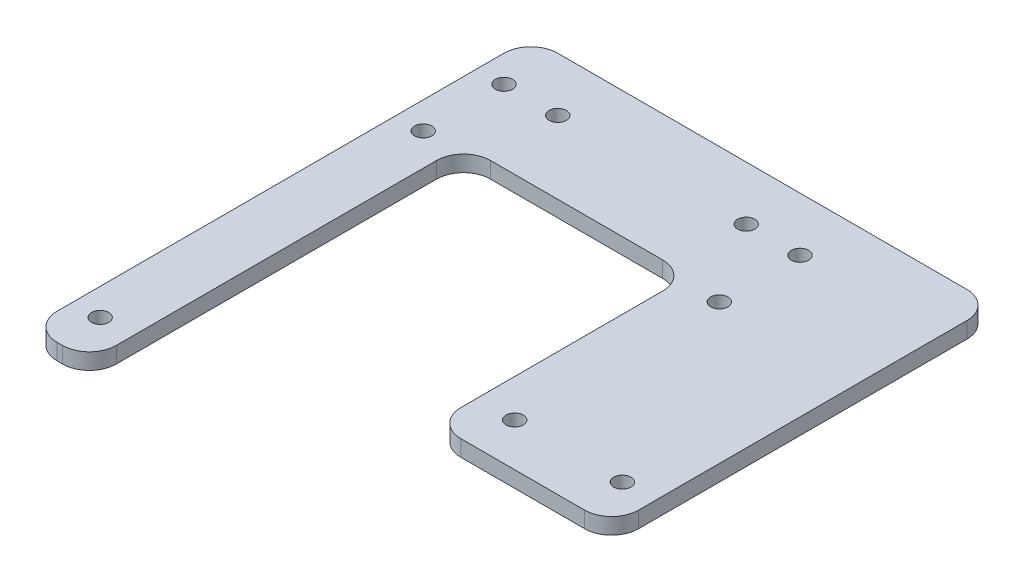
SolidWorks part; units mm, degrees
material "A-玻璃纤维"
ref_plane "前视基准面" through (0, 0, 0) normal (0, 0, 1) x (1, 0, 0)
ref_plane "上视基准面" through (0, 0, 0) normal (0, 1, 0) x (1, 0, 0)
ref_plane "右视基准面" through (0, 0, 0) normal (1, 0, 0) x (0, 0, -1)
sketch "草图1" plane through (0, 0, 0) normal (0, 1, 0) x (1, 0, 0)
  line L0 (0, 420.0815) -> (0, -400.8011) construction
  line L1 (190, 287) -> (101.545, 287)
  line L2 (190, 287) -> (190, 0)
  line L3 (190, -281) -> (144.0917, -281)
  line L4 (-190, 287) -> (-190, 0)
  line L5 (-313.6361, 0) -> (397.123, 0) construction
  line L6 (144.0917, -281) -> (98.6603, -281)
  line L7 (-101.545, 287) -> (-79.6057, 249)
  line L8 (-79.6057, 249) -> (79.6057, 249)
  line L9 (79.6057, 249) -> (101.545, 287)
  line L10 (-98.6603, -281) -> (-74.4115, -239)
  line L12 (-74.4115, -239) -> (74.4115, -239)
  line L13 (-144.0917, -281) -> (-190, -281)
  line L14 (-101.545, 287) -> (-190, 287)
  line L15 (-98.6603, -281) -> (-144.0917, -281)
  line L17 (190, 0) -> (190, -281)
  line L20 (190, 287) -> (190, -281) construction
  line L22 (74.4115, -239) -> (98.6603, -281)
  line L24 (-190, 0) -> (-190, -281)
  line L26 (-190, 287) -> (-190, -281) construction
  line L44 (229.3448, 326.3448) -> (229.3448, -320.3448) construction
  line L45 (-229.3448, 326.3448) -> (-229.3448, -320.3448) construction
  line L46 (-78.8293, 326.3448) -> (-229.3448, 326.3448) construction
  line L47 (-78.8293, 326.3448) -> (-56.89, 288.3448) construction
  line L48 (-56.89, 288.3448) -> (56.89, 288.3448) construction
  line L49 (56.89, 288.3448) -> (78.8293, 326.3448) construction
  line L50 (229.3448, 326.3448) -> (78.8293, 326.3448) construction
  line L51 (-121.376, -320.3448) -> (-229.3448, -320.3448) construction
  line L52 (229.3448, -320.3448) -> (121.376, -320.3448) construction
  line L53 (-98.6603, -281) -> (-121.376, -320.3448) construction
  line L54 (98.6603, -281) -> (121.376, -320.3448) construction
  line L55 (-132.7338, -261.3276) -> (-144.0917, -281) construction
  line L56 (-132.7338, -261.3276) -> (-97.1273, -199.6552) construction
  line L57 (-97.1273, -199.6552) -> (97.1273, -199.6552) construction
  line L58 (97.1273, -199.6552) -> (132.7338, -261.3276) construction
  line L59 (132.7338, -261.3276) -> (144.0917, -281) construction
  point P0 (0, 0)
  point P10 (-110.2073, -274)
  point P13 (-79.8964, -221.5)
  point P14 (79.8964, -221.5)
  point P16 (110.2073, -274)
  point P21 (200, -271.5)
  point P22 (200, 291.5)
  point P23 (-145.7725, 287)
  point P24 (77.0076, 246.5)
  point P25 (-77.0076, 246.5)
  point P27 (-200, 291.5)
  point P28 (-200, -271.5)
  dimension "D1" = 568
  dimension "D2" = 380
  dimension "D3" = 38
  dimension "D4" = 197.3205
  dimension "D5" = 120
  dimension "D6" = 60
  dimension "D7" = 203.09
  dimension "D8" = 42
  dimension "D9" = 287
extrude "基本板" add sketch "草图1" along normal blind 3
sketch "草图2" plane through (0, 3, 0) normal (0, 1, 0) x (1, 0, 0)
  circle A0 centre (0, 0) radius 37.5
  circle A1 centre (38.9711, 22.5) radius 1.6
  circle A3 centre (0, 0) radius 37.5
  circle A5 centre (0, -45) radius 1.6
  circle A6 centre (0, 0) radius 37.5
  circle A7 centre (-38.9711, 22.5) radius 1.6
  point P14 (0, 0)
  point P16 (0, 0)
  dimension "D1" = 75
  dimension "D3" = 3.2
  dimension "D2" = 45
  dimension "D4" = 3
extrude "云台孔" cut sketch "草图2" against normal blind 3 contours A1 | A0 | A5 | A7 region at (0, 3, 0) region at (38.9711, 3, -22.5) region at (0, 3, 45) region at (-38.9711, 3, -22.5)
sketch "草图8" plane through (0, 3, 0) normal (0, 1, 0) x (1, 0, 0)
  line L0 (0, 320.5112) -> (0, -345.0597) construction
  line L13 (82.5, -149) -> (147.5, -149)
  line L14 (-82.5, -149) -> (-147.5, -149)
  line L15 (-82.5, -149) -> (-82.5, -174)
  line L16 (-82.5, -174) -> (-147.5, -174)
  line L17 (-147.5, -149) -> (-147.5, -174)
  line L18 (-82.5, -149) -> (-147.5, -174) construction
  line L19 (-82.5, -174) -> (-147.5, -149) construction
  line L20 (147.5, -149) -> (147.5, -174)
  line L21 (82.5, -149) -> (147.5, -174) construction
  line L22 (82.5, -174) -> (147.5, -149) construction
  line L23 (82.5, -149) -> (82.5, -174)
  line L24 (82.5, -174) -> (147.5, -174)
  point P12 (-115, -161.5)
  dimension "D1" = 230
  dimension "D5" = 174
  dimension "D7" = 25
  dimension "D8" = 65
extrude "减重过线孔" cut sketch "草图8" against normal blind 3
sketch "草图41" plane through (0, 3, 0) normal (0, 1, 0) x (1, 0, 0)
  line L0 (0, 188.4867) -> (0, -152.142) construction
  line L1 (-206.7892, 0) -> (229.7274, 0) construction
  line L2 (-130, 100) -> (-75, 100)
  line L3 (-130, 100) -> (-130, 40)
  line L4 (-130, 40) -> (-75, 40)
  line L5 (-75, 100) -> (-75, 40)
  line L6 (75, 100) -> (75, 40)
  line L7 (130, 40) -> (75, 40)
  line L8 (130, 100) -> (130, 40)
  line L9 (130, 100) -> (75, 100)
  line L10 (130, -100) -> (75, -100)
  line L11 (130, -100) -> (130, -40)
  line L12 (130, -40) -> (75, -40)
  line L13 (75, -100) -> (75, -40)
  line L14 (-75, -100) -> (-75, -40)
  line L15 (-130, -40) -> (-75, -40)
  line L16 (-130, -100) -> (-130, -40)
  line L17 (-130, -100) -> (-75, -100)
  dimension "D1" = 40
  dimension "D2" = 75
  dimension "D3" = 55
  dimension "D4" = 60
extrude "减重过线孔2" cut sketch "草图41" against normal blind 10
sketch "草图10" plane through (0, 3, 0) normal (0, 1, 0) x (1, 0, 0)
  line L0 (0, 320.3944) -> (0, -95.0551) construction
  line L1 (-162.5, 182) -> (-97.5, 182)
  line L2 (-162.5, 182) -> (-162.5, 152)
  line L3 (-162.5, 152) -> (-97.5, 152)
  line L4 (-97.5, 182) -> (-97.5, 152)
  line L5 (-162.5, 182) -> (-97.5, 152) construction
  line L6 (-162.5, 152) -> (-97.5, 182) construction
  line L7 (162.5, 152) -> (97.5, 152)
  line L8 (97.5, 152) -> (97.5, 182)
  line L9 (97.5, 182) -> (162.5, 182)
  line L11 (162.5, 182) -> (162.5, 152)
  point P0 (-130, 167)
  dimension "D1" = 65
  dimension "D2" = 30
  dimension "D3" = 167
  dimension "D4" = 130
  dimension "D5" = 65
extrude "后电机过线孔" cut sketch "草图10" against normal blind 3
sketch "草图11" plane through (0, 3, 0) normal (0, 1, 0) x (1, 0, 0)
  line L0 (-190, 287) -> (-190, -281) construction
  line L1 (-179, 248) -> (-137, 248)
  line L2 (-179, 248) -> (-179, 220)
  line L3 (-179, 220) -> (-137, 220)
  line L4 (-137, 248) -> (-137, 220)
  line L5 (-179, 248) -> (-137, 220) construction
  line L6 (-179, 220) -> (-137, 248) construction
  line L8 (-158, 274.32) -> (-158, 185.5546) construction
  line L9 (-208.9066, 234) -> (-106.7696, 234) construction
  line L10 (-264.4169, 0) -> (335.6364, 0) construction
  line L11 (0, 360.1922) -> (0, -386.7193) construction
  line L12 (179, 248) -> (179, 220)
  line L13 (179, 220) -> (137, 220)
  line L14 (137, 248) -> (137, 220)
  line L15 (179, 248) -> (137, 248)
  line L16 (179, -248) -> (137, -248)
  line L17 (137, -248) -> (137, -220)
  line L18 (179, -220) -> (137, -220)
  line L19 (179, -248) -> (179, -220)
  line L20 (-179, -248) -> (-179, -220)
  line L21 (-179, -220) -> (-137, -220)
  line L22 (-137, -248) -> (-137, -220)
  line L23 (-179, -248) -> (-137, -248)
  circle A0 centre (-153.5, 259) radius 1.6
  circle A1 centre (-162.5, 259) radius 1.6
  circle A2 centre (-153.5, 209) radius 1.6
  circle A3 centre (-162.5, 209) radius 1.6
  circle A4 centre (153.5, 259) radius 1.6
  circle A5 centre (162.5, 259) radius 1.6
  circle A6 centre (153.5, 209) radius 1.6
  circle A7 centre (162.5, 209) radius 1.6
  circle A8 centre (162.5, -209) radius 1.6
  circle A9 centre (153.5, -209) radius 1.6
  circle A10 centre (162.5, -259) radius 1.6
  circle A11 centre (153.5, -259) radius 1.6
  circle A12 centre (-162.5, -209) radius 1.6
  circle A13 centre (-153.5, -209) radius 1.6
  circle A14 centre (-153.5, -259) radius 1.6
  circle A15 centre (-162.5, -259) radius 1.6
  point P0 (-158, 234)
  dimension "D5" = 3.2
  dimension "D1" = 42
  dimension "D2" = 28
  dimension "D3" = 32
  dimension "D4" = 468
  dimension "D6" = 4.5
  dimension "D7" = 25
extrude "悬挂过孔" cut sketch "草图11" against normal blind 3
sketch "草图13" plane through (0, 3, 0) normal (0, 1, 0) x (1, 0, 0)
  line L0 (79.6057, 249) -> (-79.6057, 249) construction
  line L1 (25, 226) -> (-25, 226) construction
  line L2 (25, 226) -> (25, 176) construction
  line L3 (25, 176) -> (-25, 176) construction
  line L4 (-25, 226) -> (-25, 176) construction
  line L5 (25, 226) -> (-25, 176) construction
  line L6 (25, 176) -> (-25, 226) construction
  circle A0 centre (25, 176) radius 1.6
  circle A1 centre (25, 226) radius 1.6
  circle A2 centre (-25, 226) radius 1.6
  circle A3 centre (-25, 176) radius 1.6
  point P0 (0, 201)
  dimension "D1" = 3.2
  dimension "D2" = 50
  dimension "D3" = 48
  dimension "D4" = 50
extrude "原灯柱固定孔" cut sketch "草图13" against normal blind 3
sketch "草图14" plane through (0, 3, 0) normal (0, 1, 0) x (1, 0, 0)
  line L0 (0, 388.2914) -> (0, -299.2561) construction
  line L1 (79.6057, 249) -> (-79.6057, 249) construction
  line L4 (-74.4115, -239) -> (74.4115, -239) construction
  circle A0 centre (-47.5, 239) radius 2
  circle A1 centre (-47.5, 214) radius 2
  circle A2 centre (47.5, 214) radius 2
  circle A3 centre (47.5, 239) radius 2
  circle A4 centre (-47.5, -207) radius 2
  circle A5 centre (-47.5, -232) radius 2
  circle A6 centre (47.5, -232) radius 2
  circle A7 centre (47.5, -207) radius 2
  dimension "D1" = 25
  dimension "D3" = 4
  dimension "D4" = 4
  dimension "D6" = 4
  dimension "D7" = 4
  dimension "D2" = 10
  dimension "D5" = 47.5
  dimension "D8" = 25
  dimension "D9" = 7
  dimension "D10" = 95
extrude "前后装甲板固定孔" cut sketch "草图14" against normal blind 3
sketch "草图15" plane through (0, 3, 0) normal (0, 1, 0) x (1, 0, 0)
  line L0 (-212.3646, 0) -> (277.5556, 0) construction
  line L1 (190, -281) -> (190, 287) construction
  line L2 (0, 389.4336) -> (0, -385.931) construction
  circle A0 centre (155, 47.5) radius 2
  circle A1 centre (180, 47.5) radius 2
  circle A2 centre (180, -47.5) radius 2
  circle A3 centre (155, -47.5) radius 2
  circle A4 centre (-155, -47.5) radius 2
  circle A5 centre (-180, -47.5) radius 2
  circle A6 centre (-180, 47.5) radius 2
  circle A7 centre (-155, 47.5) radius 2
  dimension "D1" = 25
  dimension "D4" = 4
  dimension "D5" = 4
  dimension "D2" = 10
  dimension "D3" = 47.5
extrude "左右装甲板固定孔" cut sketch "草图15" against normal blind 3
sketch "草图16" plane through (0, 3, 0) normal (0, 1, 0) x (1, 0, 0)
  line L0 (0, 371.6115) -> (0, -351.9198) construction
  line L1 (79.6057, 249) -> (-79.6057, 249) construction
  line L2 (-74.4115, -239) -> (74.4115, -239) construction
  circle A0 centre (-64, 229) radius 1.6
  circle A1 centre (-64, 117) radius 1.6
  circle A2 centre (-64, 5) radius 1.6
  circle A3 centre (-64, -107) radius 1.6
  circle A4 centre (-64, -219) radius 1.6
  circle A5 centre (64, 229) radius 1.6
  circle A6 centre (64, -107) radius 1.6
  circle A7 centre (64, 5) radius 1.6
  circle A8 centre (64, 117) radius 1.6
  circle A9 centre (64, -219) radius 1.6
  dimension "D1" = 20
  dimension "D2" = 3.2
  dimension "D3" = 128
  dimension "D4" = 20
  dimension "D5" = 4
  dimension "D6" = 112
  dimension "D7" = 112
extrude "加强筋固定孔" cut sketch "草图16" against normal blind 3
sketch "草图17" plane through (0, 3, 0) normal (0, 1, 0) x (1, 0, 0)
  line L0 (134.2077, 331.9193) -> (53.2432, 191.6847) construction
  line L1 (101.545, 287) -> (79.6057, 249) construction
  line L2 (190, 287) -> (101.545, 287) construction
  line L3 (0, 408.349) -> (0, -455.0242) construction
  line L4 (-45.0771, -171.5407) -> (-117.5498, -297.067) construction
  line L5 (190, -281) -> (190, 287) construction
  line L6 (-190, -281) -> (-98.6603, -281) construction
  line L7 (-190, 287) -> (-190, -281) construction
  line L8 (-98.6603, -281) -> (-74.4115, -239) construction
  circle A0 centre (95, 264.0096) radius 1.6
  circle A1 centre (102.5, 277) radius 1.6
  circle A3 centre (-95, -258.0096) radius 1.6
  circle A4 centre (-102.5, -271) radius 1.6
  circle A7 centre (102.5, -271) radius 1.6
  circle A8 centre (95, -258.0096) radius 1.6
  circle A10 centre (-102.5, 277) radius 1.6
  circle A11 centre (-95, 264.0096) radius 1.6
  dimension "D2" = 15
  dimension "D4" = 3.2
  dimension "D5" = 3.2
  dimension "D6" = 95
  dimension "D11" = 3.2
  dimension "D12" = 3.2
  dimension "D3" = 95
  dimension "D8" = 10
  dimension "D14" = 10
  dimension "D16" = 15
extrude "前后挡片固定孔" [suppressed] cut sketch "草图17" against normal blind 3
sketch "草图18" plane through (0, 3, 0) normal (0, 1, 0) x (1, 0, 0)
  line L0 (325.6997, 0) -> (-414.0484, 0) construction
  line L1 (167.6795, 77.7768) -> (228.1621, 112.6965) construction
  line L2 (190, -281) -> (190, 287) construction
  line L3 (0, 334.7186) -> (0, -324.7689) construction
  line L4 (190, -281) -> (190, 287) construction
  circle A0 centre (167.6795, 77.7768) radius 1.6
  circle A1 centre (185, 87.7768) radius 1.6
  circle A2 centre (185, -87.7768) radius 1.6
  circle A3 centre (167.6795, -77.7768) radius 1.6
  circle A4 centre (-167.6795, -77.7768) radius 1.6
  circle A5 centre (-185, -87.7768) radius 1.6
  circle A6 centre (-185, 87.7768) radius 1.6
  circle A7 centre (-167.6795, 77.7768) radius 1.6
  point P24 (190, 90.6636)
  dimension "D1" = 30
  dimension "D5" = 3.2
  dimension "D6" = 3.2
  dimension "D2" = 181.3272
  dimension "D3" = 20
  dimension "D4" = 5
extrude "左右挡片固定孔" [suppressed] cut sketch "草图18" against normal blind 3
sketch "草图19" plane through (0, 3, 0) normal (0, 1, 0) x (1, 0, 0)
  line L0 (-190, 287) -> (-190, -281) construction
  line L2 (0, 300.5357) -> (0, -347.8075) construction
  line L3 (-284.3527, 0) -> (241.9977, 0) construction
  circle A0 centre (-177.5, -78) radius 2
  circle A1 centre (-177.5, -94) radius 2.5
  circle A2 centre (-177.5, 94) radius 2.5
  circle A3 centre (-177.5, 78) radius 2
  circle A4 centre (177.5, -94) radius 2.5
  circle A5 centre (177.5, -78) radius 2
  circle A6 centre (177.5, 78) radius 2
  circle A7 centre (177.5, 94) radius 2.5
  dimension "D1" = 12.5
  dimension "D3" = 4
  dimension "D4" = 5
  dimension "D2" = 188
  dimension "D5" = 16
extrude "纵车架固定孔" cut sketch "草图19" against normal blind 3
sketch "草图21" plane through (0, 3, 0) normal (0, 1, 0) x (1, 0, 0)
  line L1 (-84.0108, 0) -> (121.9234, 0) construction
  circle A0 centre (0, -93) radius 1.6
  dimension "D1" = 186
  dimension "D2" = 3.2
extrude "横车架固定孔" cut sketch "草图21" against normal blind 3
sketch "草图30" [suppressed] plane through (0, 3, 0) normal (0, 1, 0) x (1, 0, 0)
  line L0 (0, -74.9086) -> (0, -247.6971) construction
  line L1 (65, -113) -> (65, -157)
  line L2 (-77, -110) -> (-68, -110)
  line L3 (-80, -113) -> (-80, -157)
  line L4 (-77, -160) -> (-68, -160)
  line L5 (-65, -113) -> (-65, -157)
  line L6 (77, -160) -> (68, -160)
  line L7 (80, -113) -> (80, -157)
  line L8 (77, -110) -> (68, -110)
  arc A0 (-68, -110) -> (-65, -113) centre (-68, -113) cw
  arc A1 (-80, -157) -> (-77, -160) centre (-77, -157) ccw
  arc A2 (-68, -160) -> (-65, -157) centre (-68, -157) ccw
  arc A3 (-77, -110) -> (-80, -113) centre (-77, -113) ccw
  arc A4 (77, -110) -> (80, -113) centre (77, -113) cw
  arc A5 (68, -160) -> (65, -157) centre (68, -157) cw
  arc A6 (80, -157) -> (77, -160) centre (77, -157) cw
  arc A7 (68, -110) -> (65, -113) centre (68, -113) ccw
  point P11 (-65, -110)
  point P14 (-80, -160)
  point P17 (-65, -160)
  dimension "D5" = 3
  dimension "D1" = 50
  dimension "D2" = 15
  dimension "D3" = 130
  dimension "D4" = 110
sketch "草图32" plane through (0, 3, 0) normal (0, 1, 0) x (1, 0, 0)
  line L0 (0, -130.9301) -> (0, -286.8622) construction
  line L2 (-34.5, -190) -> (34.5, -190)
  line L3 (-37.5, -187) -> (-37.5, -133)
  line L4 (-34.5, -130) -> (34.5, -130)
  line L5 (37.5, -187) -> (37.5, -133)
  line L6 (0, -130) -> (0, -190) construction
  line L7 (-37.5, -160) -> (37.5, -160) construction
  arc A0 (34.5, -190) -> (37.5, -187) centre (34.5, -187) ccw
  arc A1 (-37.5, -133) -> (-34.5, -130) centre (-34.5, -133) cw
  arc A2 (-34.5, -190) -> (-37.5, -187) centre (-34.5, -187) cw
  arc A3 (34.5, -130) -> (37.5, -133) centre (34.5, -133) cw
  point P3 (0, -160)
  point P9 (37.5, -190)
  point P15 (-37.5, -130)
  point P18 (-37.5, -190)
  dimension "D4" = 3
  dimension "D1" = 60
  dimension "D2" = 75
  dimension "D3" = 160
extrude "切除-拉伸9" cut sketch "草图32" against normal blind 10
sketch "草图33" plane through (0, 3, 0) normal (0, 1, 0) x (1, 0, 0)
  line L1 (-70.5, -55) -> (70.5, -55) construction
  line L2 (-70.5, -55) -> (-70.5, -186) construction
  line L3 (-70.5, -186) -> (70.5, -186) construction
  line L4 (70.5, -55) -> (70.5, -186) construction
  line L5 (0, -186) -> (0, -55) construction
  line L6 (-70.5, -120.5) -> (70.5, -120.5) construction
  line L7 (-60, -180.5) -> (60, -180.5) construction
  line L8 (-60, -180.5) -> (-60, -60.5) construction
  line L9 (-60, -60.5) -> (60, -60.5) construction
  line L10 (60, -180.5) -> (60, -60.5) construction
  line L11 (0, -60.5) -> (0, -180.5) construction
  line L12 (-60, -120.5) -> (60, -120.5) construction
  circle A0 centre (-60, -180.5) radius 1.6 construction
  circle A1 centre (60, -180.5) radius 1.6 construction
  circle A2 centre (60, -60.5) radius 1.6 construction
  circle A3 centre (-60, -60.5) radius 1.6 construction
  circle A4 centre (-42.5, -120.5) radius 1.6
  circle A5 centre (42.5, -120.5) radius 1.6
  point P0 (0, -120.5)
  point P4 (0, -120.5)
  dimension "D6" = 3.2
  dimension "D7" = 3.2
  dimension "D8" = 3.2
  dimension "D9" = 3.2
  dimension "D10" = 3.2
  dimension "D11" = 85
  dimension "D1" = 131
  dimension "D2" = 141
  dimension "D3" = 55
  dimension "D4" = 120
  dimension "D5" = 120
extrude "PC座固定孔" cut sketch "草图33" against normal blind 10
sketch "草图36" plane through (0, 3, 0) normal (0, 1, 0) x (1, 0, 0)
  line L0 (-237.1174, 0) -> (284.0197, 0) construction
  line L1 (0, 354.7574) -> (0, -284.8649) construction
  line L2 (-74.4115, -239) -> (74.4115, -239) construction
  line L4 (79.6057, 249) -> (-79.6057, 249) construction
  circle A0 centre (-80, -231) radius 1.6
  circle A1 centre (-80, -219) radius 1.6
  circle A2 centre (80, -219) radius 1.6
  circle A3 centre (80, -231) radius 1.6
  circle A4 centre (-80, 241) radius 1.6
  circle A5 centre (-80, 229) radius 1.6
  circle A6 centre (80, 229) radius 1.6
  circle A7 centre (80, 241) radius 1.6
  dimension "D1" = 3.2
  dimension "D2" = 3.2
  dimension "D4" = 8
  dimension "D6" = 3.2
  dimension "D3" = 12
  dimension "D5" = 160
  dimension "D7" = 8
  dimension "D9" = 160
  dimension "D10" = 12
  dimension "D8" = 2
extrude "前后防撞架固定孔" cut sketch "草图36" against normal through all
sketch "草图29" plane through (0, 3, 0) normal (0, 1, 0) x (1, 0, 0)
  line L1 (40, 98) -> (40, 142)
  line L2 (37, 95) -> (-37, 95)
  line L3 (-40, 98) -> (-40, 142)
  line L4 (37, 145) -> (-37, 145)
  line L5 (-40, 120) -> (40, 120) construction
  line L6 (0, 95) -> (0, 145) construction
  arc A0 (40, 142) -> (37, 145) centre (37, 142) ccw
  arc A1 (-37, 95) -> (-40, 98) centre (-37, 98) cw
  arc A2 (40, 98) -> (37, 95) centre (37, 98) cw
  arc A3 (-40, 142) -> (-37, 145) centre (-37, 142) cw
  circle A4 centre (48, 120) radius 1.6
  circle A5 centre (0, 86) radius 1.6
  circle A6 centre (0, 154) radius 1.6
  circle A7 centre (-48, 120) radius 1.6
  point P0 (0, 120)
  point P6 (40, 145)
  point P12 (-40, 95)
  point P15 (40, 95)
  dimension "D4" = 3
  dimension "D5" = 3.2
  dimension "D7" = 3.2
  dimension "D8" = 68
  dimension "D1" = 80
  dimension "D2" = 50
  dimension "D3" = 120
  dimension "D6" = 96
extrude "电池座固定孔" cut sketch "草图29" against normal blind 10
sketch "草图39" plane through (0, 3, 0) normal (0, 1, 0) x (1, 0, 0)
  line L0 (185, -224.8149) -> (185, -286) construction
  line L1 (190, -281) -> (190, 287) construction
  line L2 (130, -286) -> (185, -286) construction
  line L3 (98.6603, -281) -> (190, -281) construction
  line L4 (130, -224.8149) -> (130, -286) construction
  line L5 (0, -68.0168) -> (0, -303.6758) construction
  line L6 (-288.2309, 3) -> (310.1394, 3) construction
  line L7 (130, 230.8149) -> (130, 292) construction
  line L8 (130, 292) -> (185, 292) construction
  line L9 (185, 230.8149) -> (185, 292) construction
  line L10 (190, 287) -> (101.545, 287) construction
  line L11 (157.5, -286) -> (157.5, -234.7139) construction
  circle A0 centre (185, -271) radius 1.6
  circle A1 centre (185, -256) radius 1.6
  circle A2 centre (130, -256) radius 1.6
  circle A3 centre (130, -271) radius 1.6
  circle A4 centre (-130, -271) radius 1.6
  circle A5 centre (-130, -256) radius 1.6
  circle A6 centre (-185, -256) radius 1.6
  circle A7 centre (-185, -271) radius 1.6
  circle A8 centre (-130, 262) radius 1.6
  circle A9 centre (-130, 277) radius 1.6
  circle A10 centre (185, 262) radius 1.6
  circle A11 centre (185, 277) radius 1.6
  circle A12 centre (-185, 277) radius 1.6
  circle A13 centre (-185, 262) radius 1.6
  circle A14 centre (130, 277) radius 1.6
  circle A15 centre (130, 262) radius 1.6
  dimension "D3" = 3.2
  dimension "D4" = 15
  dimension "D5" = 15
  dimension "D8" = 5
  dimension "D1" = 5
  dimension "D2" = 5
  dimension "D6" = 55
extrude "对角防撞架固定孔" cut sketch "草图39" against normal blind 10
sketch "草图42" plane through (0, 3, 0) normal (0, 1, 0) x (1, 0, 0)
  line L0 (-25, 226) -> (25, 176) construction
  line L1 (-25, 176) -> (25, 226) construction
  line L3 (-20, 221) -> (20, 221)
  line L4 (-20, 221) -> (-20, 181)
  line L5 (-20, 181) -> (20, 181)
  line L6 (20, 221) -> (20, 181)
  line L7 (0, 181) -> (0, 221) construction
  line L8 (-20, 201) -> (20, 201) construction
  point P8 (0, 201)
  dimension "D1" = 40
extrude "切除-拉伸11" cut sketch "草图42" against normal blind 10
sketch "草图43" plane through (0, 3, 0) normal (0, 1, 0) x (1, 0, 0)
  line L0 (0, 69.935) -> (0, -77.0754) construction
  line L1 (-56.3274, 0) -> (63.1225, 0) construction
  line L32 (75, 32.5) -> (75, -32.5) construction
  line L33 (81, 32.5) -> (81, -32.5)
  line L34 (69, 32.5) -> (69, -32.5)
  line L35 (95, 32.5) -> (95, -32.5) construction
  line L36 (101, 32.5) -> (101, -32.5)
  line L37 (89, 32.5) -> (89, -32.5)
  line L38 (115, 32.5) -> (115, -32.5) construction
  line L39 (121, 32.5) -> (121, -32.5)
  line L40 (109, 32.5) -> (109, -32.5)
  line L41 (135, 32.5) -> (135, -32.5) construction
  line L42 (141, 32.5) -> (141, -32.5)
  line L43 (129, 32.5) -> (129, -32.5)
  line L44 (-75, 32.5) -> (-75, -32.5) construction
  line L45 (-81, 32.5) -> (-81, -32.5)
  line L46 (-69, 32.5) -> (-69, -32.5)
  line L47 (-95, 32.5) -> (-95, -32.5) construction
  line L48 (-101, 32.5) -> (-101, -32.5)
  line L49 (-89, 32.5) -> (-89, -32.5)
  line L50 (-115, 32.5) -> (-115, -32.5) construction
  line L51 (-121, 32.5) -> (-121, -32.5)
  line L52 (-109, 32.5) -> (-109, -32.5)
  line L53 (-135, 32.5) -> (-135, -32.5) construction
  line L54 (-141, 32.5) -> (-141, -32.5)
  line L55 (-129, 32.5) -> (-129, -32.5)
  arc A0 (81, 32.5) -> (69, 32.5) centre (75, 32.5) ccw
  arc A1 (69, -32.5) -> (81, -32.5) centre (75, -32.5) ccw
  arc A5 (101, 32.5) -> (89, 32.5) centre (95, 32.5) ccw
  arc A6 (89, -32.5) -> (101, -32.5) centre (95, -32.5) ccw
  arc A7 (121, 32.5) -> (109, 32.5) centre (115, 32.5) ccw
  arc A8 (109, -32.5) -> (121, -32.5) centre (115, -32.5) ccw
  arc A9 (141, 32.5) -> (129, 32.5) centre (135, 32.5) ccw
  arc A10 (129, -32.5) -> (141, -32.5) centre (135, -32.5) ccw
  arc A11 (-81, 32.5) -> (-69, 32.5) centre (-75, 32.5) cw
  arc A12 (-69, -32.5) -> (-81, -32.5) centre (-75, -32.5) cw
  arc A13 (-101, 32.5) -> (-89, 32.5) centre (-95, 32.5) cw
  arc A14 (-89, -32.5) -> (-101, -32.5) centre (-95, -32.5) cw
  arc A15 (-121, 32.5) -> (-109, 32.5) centre (-115, 32.5) cw
  arc A16 (-109, -32.5) -> (-121, -32.5) centre (-115, -32.5) cw
  arc A17 (-141, 32.5) -> (-129, 32.5) centre (-135, 32.5) cw
  arc A18 (-129, -32.5) -> (-141, -32.5) centre (-135, -32.5) cw
  point P4 (75, 0)
  point P16 (95, 0)
  point P23 (115, 0)
  point P30 (135, 0)
  point P35 (-75, 0)
  point P42 (-95, 0)
  point P49 (-115, 0)
  point P57 (-135, 0)
  dimension "D1" = 4
  dimension "D4" = 75
  dimension "D5" = 20
  dimension "D2" = 12
  dimension "D3" = 65
extrude "切除-拉伸12" [suppressed] cut sketch "草图43" against normal blind 10
sketch "草图44" [suppressed] plane through (0, 3, 0) normal (0, 1, 0) x (1, 0, 0)
  line L0 (0, 99.1729) -> (0, -37.5) construction
  circle A0 centre (115, -264) radius 1.6
  circle A3 centre (185, -264) radius 1.6 construction
  circle A4 centre (185, -264) radius 1.6
  circle A5 centre (0, 0) radius 37.5 construction
  circle A6 centre (185, -231) radius 1.6
  circle A7 centre (185, 284) radius 1.6 construction
  circle A8 centre (185, 284) radius 1.6
  circle A9 centre (-115, -264) radius 1.6
  circle A10 centre (-185, -231) radius 1.6
  circle A11 centre (115, 284) radius 1.6
  circle A12 centre (185, 241) radius 1.6
  circle A13 centre (-185, 241) radius 1.6
  circle A14 centre (-115, 284) radius 1.6
  point P15 (0, 30.8364)
  dimension "D1" = 3.2
  dimension "D3" = 3.2
  dimension "D5" = 3.2
  dimension "D6" = 3.2
  dimension "D2" = 70
  dimension "D4" = 33
  dimension "D7" = 43
  dimension "D8" = 70
extrude "切除-拉伸13" [suppressed] cut sketch "草图44" against normal through all
sketch "草图34" plane through (0, 3, 0) normal (0, 1, 0) x (1, 0, 0)
  line L1 (71, 206) -> (109, 206) construction
  line L2 (71, 206) -> (71, 168) construction
  line L3 (71, 168) -> (109, 168) construction
  line L4 (109, 206) -> (109, 168) construction
  line L5 (90, 168) -> (90, 206) construction
  line L6 (71, 187) -> (109, 187) construction
  circle A0 centre (90, 168) radius 1.6
  circle A1 centre (71, 187) radius 1.6
  circle A2 centre (90, 206) radius 1.6
  circle A3 centre (109, 187) radius 1.6
  point P0 (90, 187)
  dimension "D2" = 3.2
  dimension "D3" = 3.2
  dimension "D4" = 3.2
  dimension "D7" = 3.2
  dimension "D1" = 38
  dimension "D5" = 90
  dimension "D6" = 187
extrude "UWB固定孔" cut sketch "草图34" against normal blind 10
sketch "草图47" plane through (0, 3, 0) normal (0, 1, 0) x (1, 0, 0)
  line L0 (0, 349.8553) -> (0, -296.5751) construction
  circle A0 centre (140, 277) radius 1.6
  circle A1 centre (185, -271) radius 1.6 construction
  circle A2 centre (185, -271) radius 1.6
  circle A3 centre (95, -231) radius 1.6
  circle A4 centre (175, -271) radius 1.6
  circle A5 centre (140, 213) radius 1.6
  circle A6 centre (175, -207) radius 1.6
  circle A7 centre (-140, -271) radius 1.6
  circle A8 centre (-140, -207) radius 1.6
  circle A9 centre (-175, 213) radius 1.6
  circle A10 centre (-95, 237) radius 1.6
  circle A11 centre (185, 277) radius 1.6 construction
  circle A12 centre (185, 277) radius 1.6
  circle A13 centre (175, 277) radius 1.6
  circle A14 centre (95, 237) radius 1.6
  circle A15 centre (175, 213) radius 1.6
  circle A16 centre (-175, 277) radius 1.6
  circle A17 centre (-185, 277) radius 1.6
  circle A18 centre (140, -207) radius 1.6
  circle A19 centre (140, -271) radius 1.6
  circle A20 centre (-175, -207) radius 1.6
  circle A21 centre (-140, 213) radius 1.6
  circle A22 centre (-175, -271) radius 1.6
  circle A23 centre (-95, -231) radius 1.6
  circle A24 centre (-185, -271) radius 1.6
  circle A25 centre (-140, 277) radius 1.6
  dimension "D3" = 3.2
  dimension "D6" = 3.2
  dimension "D8" = 64
  dimension "D10" = 3.2
  dimension "D13" = 3.2
  dimension "D2" = 3.2
  dimension "D9" = 3.2
  dimension "D16" = 2
  dimension "D19" = 35
  dimension "D4" = 80
  dimension "D5" = 40
  dimension "D7" = 64
  dimension "D11" = 40
  dimension "D12" = 80
  dimension "D14" = 10
  dimension "D15" = 10
  dimension "D17" = 35
  dimension "D18" = 2
extrude "救援固定孔" cut sketch "草图47" against normal through all
sketch "草图48" plane through (0, 3, 0) normal (0, 1, 0) x (1, 0, 0)
  line L0 (0, 63.9696) -> (0, -155.8034) construction
  circle A0 centre (-44.5, -46) radius 1.6
  circle A1 centre (44.5, -46) radius 1.6
  circle A2 centre (-9, -196) radius 1.6
  circle A3 centre (9, -196) radius 1.6
  dimension "D3" = 3.2
  dimension "D6" = 3.2
  dimension "D1" = 44.5
  dimension "D2" = 46
  dimension "D4" = 9
  dimension "D5" = 196
extrude "切除-拉伸14" cut sketch "草图48" against normal through all
sketch "草图50" plane through (0, 0, 0) normal (0, -1, 0) x (1, 0, 0)
  circle A0 centre (-99.3301, -275.8397) radius 1.5 construction
  circle A1 centre (-91.8301, -262.8494) radius 1.5 construction
  circle A2 centre (99.3301, -275.8397) radius 1.5 construction
  circle A3 centre (91.8301, -262.8494) radius 1.5 construction
  circle A4 centre (-99.3301, 269.8397) radius 1.5 construction
  circle A5 centre (-91.8301, 256.8494) radius 1.5 construction
  circle A6 centre (91.8301, 256.8494) radius 1.5 construction
  circle A7 centre (99.3301, 269.8397) radius 1.5 construction
  circle A8 centre (-99.3301, -275.8397) radius 1.5
  circle A9 centre (-91.8301, -262.8494) radius 1.5
  circle A10 centre (99.3301, -275.8397) radius 1.5
  circle A11 centre (91.8301, -262.8494) radius 1.5
  circle A12 centre (-99.3301, 269.8397) radius 1.5
  circle A13 centre (-91.8301, 256.8494) radius 1.5
  circle A14 centre (91.8301, 256.8494) radius 1.5
  circle A15 centre (99.3301, 269.8397) radius 1.5
extrude "切除-拉伸16" [suppressed] cut sketch "草图50" against normal blind 10
sketch "草图51" plane through (0, 3, 0) normal (0, 1, 0) x (1, 0, 0)
  line L0 (0, -15.6528) -> (0, -161.3511) construction
  line L2 (-20.5, 67.5) -> (20.5, 67.5)
  line L3 (-22.5, 65.5) -> (-22.5, 54.5)
  line L4 (-20.5, 52.5) -> (20.5, 52.5)
  line L5 (22.5, 65.5) -> (22.5, 54.5)
  line L6 (0, 52.5) -> (0, 67.5) construction
  line L7 (-22.5, 60) -> (22.5, 60) construction
  arc A0 (20.5, 67.5) -> (22.5, 65.5) centre (20.5, 65.5) cw
  arc A1 (-22.5, 54.5) -> (-20.5, 52.5) centre (-20.5, 54.5) ccw
  arc A2 (-20.5, 67.5) -> (-22.5, 65.5) centre (-20.5, 65.5) ccw
  arc A3 (20.5, 52.5) -> (22.5, 54.5) centre (20.5, 54.5) ccw
  point P3 (0, 60)
  point P9 (22.5, 67.5)
  point P15 (-22.5, 52.5)
  point P18 (-22.5, 67.5)
  dimension "D4" = 2
  dimension "D5" = 2
  dimension "D6" = 2
  dimension "D7" = 2
  dimension "D1" = 15
  dimension "D2" = 45
  dimension "D3" = 60
extrude "6623电机过线孔" cut sketch "草图51" against normal blind 10
fillet "外圆角" radius 5 12 edges at (-190, 1.5, -287) (-101.545, 1.5, -287) (-79.6057, 1.5, -249) (79.6057, 1.5, -249) (101.545, 1.5, -287) (190, 1.5, -287) (190, 1.5, 281) (98.6603, 1.5, 281) (74.4115, 1.5, 239) (-74.4115, 1.5, 239) (-98.6603, 1.5, 281) (-190, 1.5, 281)
fillet "内圆角" radius 2 52 edges at (-147.5, 1.5, 149) (-82.5, 1.5, 149) (-82.5, 1.5, 174) (-147.5, 1.5, 174) (82.5, 1.5, 149) (147.5, 1.5, 149) (147.5, 1.5, 174) (82.5, 1.5, 174) (-130, 1.5, -100) (-75, 1.5, -100) (-75, 1.5, -40) (-130, 1.5, -40) (-130, 1.5, 100) (-130, 1.5, 40) (-75, 1.5, 40) (-75, 1.5, 100) (130, 1.5, 100) (75, 1.5, 100) (75, 1.5, 40) (130, 1.5, 40) (130, 1.5, -100) (130, 1.5, -40) (75, 1.5, -40) (75, 1.5, -100) (-97.5, 1.5, -152) (-162.5, 1.5, -152) (-162.5, 1.5, -182) (-97.5, 1.5, -182) (162.5, 1.5, -182) (-137, 1.5, -220) (-179, 1.5, -220) (-179, 1.5, -248) (-137, 1.5, -248) (-179, 1.5, 220) (-137, 1.5, 220) (-137, 1.5, 248) (179, 1.5, 248) (137, 1.5, 248) (137, 1.5, 220) (179, 1.5, 220) (179, 1.5, -248) (179, 1.5, -220) (137, 1.5, -220) (137, 1.5, -248) (20, 1.5, -181) (-20, 1.5, -181) (-20, 1.5, -221) (20, 1.5, -221) (-179, 1.5, 248) (162.5, 1.5, -152) (97.5, 1.5, -152) (97.5, 1.5, -182)
sketch "草图52" plane through (0, 3, 0) normal (0, 1, 0) x (1, 0, 0)
  line L0 (0, 174.243) -> (0, -94.6) construction
  line L1 (80, 190) -> (80, 208) construction
  line L2 (-125.2, 190) -> (-80, 190) construction
  line L3 (-125.2, 190) -> (-125.2, 208) construction
  line L4 (-125.2, 208) -> (-80, 208) construction
  line L5 (-80, 190) -> (-80, 208) construction
  line L6 (125.2, 208) -> (80, 208) construction
  line L7 (125.2, 190) -> (125.2, 208) construction
  line L8 (125.2, 190) -> (80, 190) construction
  line L13 (-85, -130) -> (-130.2, -130) construction
  line L14 (85, -121) -> (130.2, -121) construction
  line L15 (85, -121) -> (85, -139) construction
  line L16 (85, -139) -> (130.2, -139) construction
  line L17 (130.2, -121) -> (130.2, -139) construction
  line L18 (107.6, -139) -> (107.6, -121) construction
  line L19 (85, -130) -> (130.2, -130) construction
  line L20 (-107.6, -139) -> (-107.6, -121) construction
  line L21 (-130.2, -121) -> (-130.2, -139) construction
  line L22 (-85, -139) -> (-130.2, -139) construction
  line L23 (-85, -121) -> (-85, -139) construction
  line L24 (-85, -121) -> (-130.2, -121) construction
  circle A0 centre (-125.2, 190) radius 1.6
  circle A1 centre (-80, 190) radius 1.6
  circle A2 centre (-80, 208) radius 1.6
  circle A3 centre (-125.2, 208) radius 1.6
  circle A4 centre (125.2, 208) radius 1.6
  circle A5 centre (80, 208) radius 1.6
  circle A6 centre (80, 190) radius 1.6
  circle A7 centre (125.2, 190) radius 1.6
  circle A9 centre (85, -139) radius 1.6
  circle A10 centre (130.2, -139) radius 1.6
  circle A11 centre (130.2, -121) radius 1.6
  circle A12 centre (85, -121) radius 1.6
  circle A13 centre (-85, -121) radius 1.6
  circle A14 centre (-130.2, -121) radius 1.6
  circle A15 centre (-130.2, -139) radius 1.6
  circle A16 centre (-85, -139) radius 1.6
  circle A17 centre (0, -93) radius 1.6 construction
  point P29 (107.6, -130)
  point P55 (-106.25, -130)
  dimension "D3" = 2
  dimension "D10" = 3.2
  dimension "D4" = 2
  dimension "D2" = 3.2
  dimension "D6" = 2
  dimension "D7" = 45.2
  dimension "D8" = 18
  dimension "D9" = 45.2
  dimension "D13" = 2
  dimension "D11" = 170
  dimension "D12" = 130
  dimension "D14" = 80
  dimension "D5" = 18
  dimension "D15" = 190
extrude "3508电调固定孔" [suppressed] cut sketch "草图52" against normal blind 10
sketch "草图53" plane through (0, 3, 0) normal (0, 1, 0) x (1, 0, 0)
  line L0 (0, -84.1974) -> (0, 49.8195) construction
  line L1 (-135, 31) -> (-85, 31) construction
  line L2 (-135, 31) -> (-135, -31) construction
  line L3 (-135, -31) -> (-85, -31) construction
  line L4 (-85, 31) -> (-85, -31) construction
  line L5 (-110, -31) -> (-110, 31) construction
  line L6 (-135, 0) -> (-85, 0) construction
  line L7 (135, 0) -> (85, 0) construction
  line L8 (110, -31) -> (110, 31) construction
  line L9 (85, 31) -> (85, -31) construction
  line L10 (135, -31) -> (85, -31) construction
  line L11 (135, 31) -> (135, -31) construction
  line L12 (135, 31) -> (85, 31) construction
  circle A0 centre (-135, -31) radius 1.6
  circle A1 centre (-85, -31) radius 1.6
  circle A2 centre (-85, 31) radius 1.6
  circle A3 centre (-135, 31) radius 1.6
  circle A4 centre (135, 31) radius 1.6
  circle A5 centre (85, 31) radius 1.6
  circle A6 centre (85, -31) radius 1.6
  circle A7 centre (135, -31) radius 1.6
  point P0 (-110, 0)
  point P26 (110, 0)
  dimension "D3" = 3.2
  dimension "D1" = 62
  dimension "D2" = 50
  dimension "D4" = 110
extrude "RFID固定孔" cut sketch "草图53" against normal blind 10
sketch "草图54" plane through (0, 0, 0) normal (0, -1, 0) x (1, 0, 0)
  line L0 (-263.9822, -3) -> (389.5678, -3) construction
  line L1 (0, -107.2403) -> (0, -312.9663) construction
  line L2 (-102.1224, -278) -> (-92.1224, -260.6795) construction
  line L3 (-81.0491, -251.5) -> (-100.1016, -284.5) construction
  line L4 (-104.4318, -287) -> (-185, -287) construction
  line L5 (102.1224, -278) -> (92.1224, -260.6795) construction
  line L6 (102.1224, 272) -> (92.1224, 254.6795) construction
  line L7 (-102.1224, 272) -> (-92.1224, 254.6795) construction
  line L8 (-185, 281) -> (-101.547, 281) construction
  circle A0 centre (-102.1224, -278) radius 1.6
  circle A1 centre (-92.1224, -260.6795) radius 1.6
  circle A2 centre (92.1224, -260.6795) radius 1.6
  circle A3 centre (102.1224, -278) radius 1.6
  circle A4 centre (102.1224, 272) radius 1.6
  circle A5 centre (92.1224, 254.6795) radius 1.6
  circle A6 centre (-92.1224, 254.6795) radius 1.6
  circle A7 centre (-102.1224, 272) radius 1.6
  dimension "D1" = 3.2
  dimension "D2" = 3.2
  dimension "D3" = 5
  dimension "D4" = 9
  dimension "D5" = 20
  dimension "D6" = 9
extrude "挡片固定孔" cut sketch "草图54" against normal blind 10
sketch "草图55" plane through (0, 0, 0) normal (0, -1, 0) x (1, 0, 0)
  line L0 (-190, -194) -> (-125, -194)
  line L1 (-125, -194) -> (-87, -230)
  line L2 (-87, -230) -> (-87, -261.8073)
  line L3 (-81.0491, -251.5) -> (-100.1016, -284.5) construction
  line L4 (-87, -261.8073) -> (-100.1016, -284.5)
  line L12 (-190, 276) -> (-190, -282)
  line L13 (-185, -287) -> (-104.4318, -287)
  line L14 (-100.1016, -284.5) -> (-81.0491, -251.5)
  line L15 (-76.7189, -249) -> (76.7189, -249)
  line L16 (81.0491, -251.5) -> (100.1016, -284.5)
  line L17 (104.4318, -287) -> (185, -287)
  line L18 (190, -282) -> (190, 276)
  line L19 (185, 281) -> (101.547, 281)
  line L20 (97.2169, 278.5) -> (75.8549, 241.5)
  line L21 (71.5248, 239) -> (-71.5248, 239)
  line L22 (-75.8549, 241.5) -> (-97.2169, 278.5)
  line L23 (-101.547, 281) -> (-185, 281)
  line L24 (-190, -194) -> (-190, -282)
  line L25 (-185, -287) -> (-104.4318, -287)
  circle A1 centre (-162.5, -209) radius 1.6 construction
  arc A2 (-100.1016, -284.5) -> (-104.4318, -287) centre (-104.4318, -282) cw
  arc A12 (-190, -282) -> (-185, -287) centre (-185, -282) ccw
  arc A13 (-104.4318, -287) -> (-100.1016, -284.5) centre (-104.4318, -282) ccw
  arc A14 (-76.7189, -249) -> (-81.0491, -251.5) centre (-76.7189, -254) ccw
  arc A15 (81.0491, -251.5) -> (76.7189, -249) centre (76.7189, -254) ccw
  arc A16 (100.1016, -284.5) -> (104.4318, -287) centre (104.4318, -282) ccw
  arc A17 (185, -287) -> (190, -282) centre (185, -282) ccw
  arc A18 (190, 276) -> (185, 281) centre (185, 276) ccw
  arc A19 (101.547, 281) -> (97.2169, 278.5) centre (101.547, 276) ccw
  arc A20 (71.5248, 239) -> (75.8549, 241.5) centre (71.5248, 244) ccw
  arc A21 (-75.8549, 241.5) -> (-71.5248, 239) centre (-71.5248, 244) ccw
  arc A22 (-97.2169, 278.5) -> (-101.547, 281) centre (-101.547, 276) ccw
  arc A23 (-185, 281) -> (-190, 276) centre (-185, 276) ccw
  arc A24 (-190, -282) -> (-185, -287) centre (-185, -282) ccw
  dimension "D2" = 65
  dimension "D1" = 0
  dimension "D3" = 15
  dimension "D4" = 57
  dimension "D5" = 103
extrude "切除-拉伸17" cut sketch "草图55" against normal blind 10 flip side to cut
fillet "圆角1" radius 5 4 edges at (-190, 1.5, -194) (-87, 1.5, -261.8073) (-87, 1.5, -230) (-125, 1.5, -194)
sketch "草图56" plane through (0, 0, 0) normal (0, -1, 0) x (1, 0, 0)
  line L0 (-190, -282) -> (-190, -199) construction
  line L1 (-158, -248) -> (-158, -229.0679) construction
  line L2 (-139, -248) -> (-177, -248) construction
  circle A0 centre (-185, -202) radius 1.6
  circle A1 centre (-185, -262) radius 1.6 construction
  circle A2 centre (-131, -202) radius 1.6
  dimension "D1" = 3.2
  dimension "D2" = 5
  dimension "D3" = 60
extrude "切除-拉伸18" cut sketch "草图56" against normal blind 10
sketch "草图57" plane through (0, 0, 0) normal (0, -1, 0) x (1, 0, 0)
  line L0 (-158, -202.9943) -> (-158, -273.4806) construction
  line L1 (-137, -222) -> (-137, -246) construction
  line L2 (-166, -204.5) -> (-150, -204.5)
  line L3 (-166, -204.5) -> (-166, -263.5)
  line L4 (-166, -263.5) -> (-150, -263.5)
  line L5 (-150, -204.5) -> (-150, -263.5)
  line L6 (-158, -263.5) -> (-158, -204.5) construction
  line L7 (-166, -234) -> (-150, -234) construction
  line L8 (-177, -220) -> (-139, -220) construction
  point P2 (-158, -234)
  point P8 (-137, -234)
  point P14 (-158, -220)
  dimension "D1" = 16
  dimension "D2" = 59
extrude "切除-拉伸19" cut sketch "草图57" against normal blind 10
sketch "草图58" plane through (0, 0, 0) normal (0, -1, 0) x (1, 0, 0)
  line L0 (-150, -263.5) -> (-150, -248) construction
  line L1 (-150, -204.5) -> (-166, -204.5) construction
  line L2 (-166, -204.5) -> (-166, -220) construction
  line L3 (-166, -248) -> (-166, -263.5) construction
  circle A0 centre (-150, -261.95) radius 1.55
  circle A1 centre (-166, -261.95) radius 1.55
  circle A2 centre (-166, -206.05) radius 1.55
  circle A3 centre (-150, -206.05) radius 1.55
  dimension "D1" = 3.1
  dimension "D2" = 2
  dimension "D3" = 2
extrude "切除-拉伸20" cut sketch "草图58" against normal blind 10
fillet "圆角2" radius 2 4 edges at (-150, 1.5, -248) (-166, 1.5, -248) (-150, 1.5, -220) (-166, 1.5, -220)
sketch "草图59" plane through (0, 0, 0) normal (0, -1, 0) x (1, 0, 0)
  line L0 (-126.9924, -194) -> (-185, -194) construction
  line L1 (-179, -263.5) -> (-137, -263.5)
  line L2 (-179, -263.5) -> (-179, -194)
  line L3 (-179, -194) -> (-137, -194)
  line L4 (-137, -263.5) -> (-137, -194)
  line L5 (-137, -222) -> (-137, -246) construction
  line L6 (-179, -246) -> (-179, -222) construction
  line L7 (-166, -263.5) -> (-150, -263.5) construction
extrude "切除-拉伸21" cut sketch "草图59" against normal blind 10
sketch "草图61" plane through (0, 0, 0) normal (0, -1, 0) x (1, 0, 0)
  line L0 (-104.4318, -287) -> (-185, -287) construction
  line L1 (-104, -194) -> (-72.4732, -194)
  line L2 (-104, -194) -> (-104, -287)
  line L3 (-104, -287) -> (-72.4732, -287)
  line L4 (-72.4732, -194) -> (-72.4732, -287)
  line L5 (-126.9924, -194) -> (-137, -194) construction
  line L6 (-137, -194) -> (-137, -263.5) construction
  dimension "D1" = 33
extrude "切除-拉伸23" cut sketch "草图61" against normal blind 10
sketch "草图62" plane through (0, 0, 0) normal (0, -1, 0) x (1, 0, 0)
  line L0 (-104, -213.8947) -> (-104, -286.9813) construction
  line L1 (-104, -216) -> (-137, -216)
  line L2 (-104, -216) -> (-104, -194)
  line L3 (-104, -194) -> (-137, -194)
  line L4 (-137, -216) -> (-137, -194)
  dimension "D1" = 22
extrude "切除-拉伸24" cut sketch "草图62" against normal blind 10
fillet "圆角3" radius 5 6 edges at (-137, 1.5, -263.5) (-179, 1.5, -263.5) (-104, 1.5, -286.9813) (-104, 1.5, -216) (-137, 1.5, -216) (-179, 1.5, -194)
sketch "草图63" plane through (0, 0, 0) normal (0, -1, 0) x (1, 0, 0)
  line L0 (-137, -221) -> (-137, -258.5) construction
  line L1 (-132, -216) -> (-109, -216) construction
  circle A0 centre (-130, -224) radius 1.6
  circle A1 centre (-110, -224) radius 1.6
  dimension "D1" = 3.2
  dimension "D2" = 7
  dimension "D3" = 8
  dimension "D4" = 2
extrude "切除-拉伸25" cut sketch "草图63" against normal blind 10
